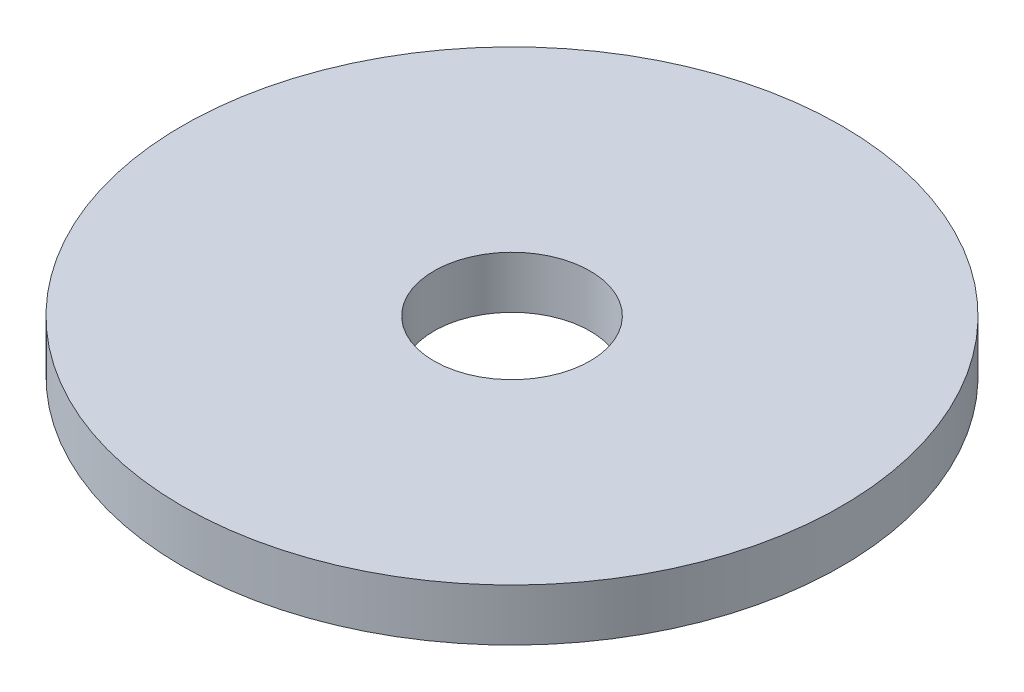
SolidWorks part; units mm, degrees
ref_plane "Front Plane" through (0, 0, 0) normal (0, 0, 1) x (1, 0, 0)
ref_plane "Top Plane" through (0, 0, 0) normal (0, 1, 0) x (1, 0, 0)
ref_plane "Right Plane" through (0, 0, 0) normal (1, 0, 0) x (0, 0, -1)
sketch "Sketch1" plane through (0, 0, 0) normal (0, 1, 0) x (1, 0, 0)
  circle A0 centre (0, 0) radius 95
  dimension "FLANGE_OD" = 190
extrude "Boss-Extrude1" add sketch "Sketch1" along normal blind 15
sketch "Sketch2" plane through (0, 0, 0) normal (0, 1, 0) x (1, 0, 0)
  circle A0 centre (0, 0) radius 22.5
  dimension "BORE_D" = 45
extrude "Cut-Extrude1" cut sketch "Sketch2" along normal through all
sketch "Sketch3" plane through (0, 15, 0) normal (0, 1, 0) x (1, 0, 0)
  circle A0 centre (0, 0) radius 19.5994 construction
  circle A1 centre (-19.5994, 0) radius 2.1464
  dimension "BOLT_D" = 4.2928
  dimension "BOLT_PCD" = 39.1988
extrude "Cut-Extrude2" cut sketch "Sketch3" against normal blind 13.018 rebuild error yes
pattern_circular "CirPattern1" count 8 over 360 rebuild error yes
